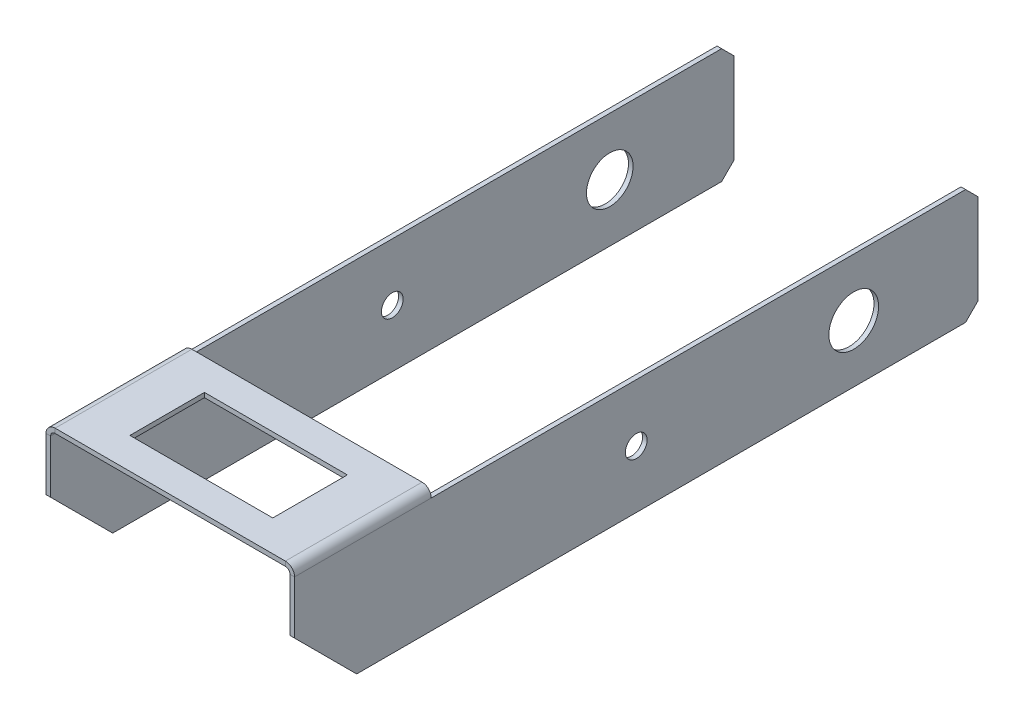
SolidWorks part; units mm, degrees
note: The reader was unsure of these and kept them because the rebuilt part matched: flange length of "Edge-Flange2".
ref_plane "Front Plane" through (0, 0, 0) normal (0, 0, 1) x (1, 0, 0)
ref_plane "Top Plane" through (0, 0, 0) normal (0, 1, 0) x (1, 0, 0)
ref_plane "Right Plane" through (0, 0, 0) normal (1, 0, 0) x (0, 0, -1)
sketch "Sketch1" plane through (0, 0, 0) normal (0, 1, 0) x (1, 0, 0)
  line L1 (-20, -11) -> (20, -11)
  line L2 (-20, -11) -> (-20, 11)
  line L3 (-20, 11) -> (20, 11)
  line L4 (20, -11) -> (20, 11)
  line L5 (-20, -11) -> (20, 11) construction
  line L6 (-20, 11) -> (20, -11) construction
  point P0 (0, 0)
  dimension "D1" = 40
  dimension "D2" = 22
base flange "Base-Flange2" sketch "Sketch1" thickness 0.7366 reverse thickness direction yes parameters "D1"=0.7366
edge flange "Edge-Flange2" sketch "Sketch30" flange profiles "Sketch30", "Sketch31" flange angle 90 flange length 20 flange position material inside bend radius 0.7366 thickness 0.7366 relief rectangular parameters "D6"=10, "D8"=1
sketch "Sketch30" plane through (20, 0, 0) normal (-1, 0, 0) x (0, 0, -1)
  line L2 (-11, 0) -> (-11, 19.2634)
  line L3 (-11, 19.2634) -> (99, 19.2634)
  line L4 (99, 19.2634) -> (99, 0)
  line L5 (11, 0) -> (-11, 0) construction
  line L6 (99, 0) -> (-11, 0)
  dimension "D1" = 110
sketch "Sketch31" plane through (-20, 0, 0) normal (1, 0, 0) x (0, 0, 1)
  line L0 (11, 0) -> (-11, 0) construction
  line L1 (11, 0) -> (-99, 0)
  line L2 (11, 0) -> (11, 19.2634)
  line L3 (11, 19.2634) -> (-99, 19.2634)
  line L4 (-99, 19.2634) -> (-99, 0)
  dimension "D1" = 110
bend "EdgeBend3" bend radius 0.7366 bend angle 90 parameters "D5"=1
bend "EdgeBend4" bend radius 0.7366 bend angle 90 parameters "D5"=2
sketch "Sketch32" plane through (-20, 0, 0) normal (-1, 0, 0) x (0, 0, 1)
  line L0 (-99, -19.2634) -> (-99, -0.7366) construction
  line L1 (-99, -10) -> (11, -10) construction
  line L2 (11, -0.7366) -> (11, -19.2634) construction
  circle A0 centre (-79, -10) radius 3.75
  circle A1 centre (-44, -10) radius 1.75
  dimension "D1" = 7.5
  dimension "D3" = 3.5
  dimension "D2" = 90
extrude "Cut-Extrude1" cut sketch "Sketch32" against normal blind 2 normal cut yes
sketch "Sketch33" plane through (20, 0, 0) normal (1, 0, 0) x (0, 0, -1)
  line L0 (99, -19.2634) -> (99, -0.7366) construction
  line L1 (99, -10) -> (-11, -10) construction
  line L2 (-11, -19.2634) -> (-11, -0.7366) construction
  circle A0 centre (44, -10) radius 1.75
  circle A1 centre (79, -10) radius 4
  dimension "D1" = 3.5
  dimension "D2" = 8
  dimension "D3" = 90
extrude "Cut-Extrude2" cut sketch "Sketch33" against normal blind 2 normal cut yes
chamfer "Chamfer1" distance 2 angle 45 4 edges at (-19.6317, -19.2634, -99) (19.6317, -19.2634, -99) (19.6317, -0.7366, -99) (-19.6317, -0.7366, -99)
chamfer "Chamfer2" distance 10 angle 45 2 edges at (-19.6317, -19.2634, 11) (19.6317, -19.2634, 11)
sketch "Sketch34" plane through (0, 0.7366, 0) normal (0, 1, 0) x (1, 0, 0)
  line L1 (-11.5, -6) -> (11.5, -6)
  line L2 (-11.5, -6) -> (-11.5, 6)
  line L3 (-11.5, 6) -> (11.5, 6)
  line L4 (11.5, -6) -> (11.5, 6)
  line L5 (-11.5, -6) -> (11.5, 6) construction
  line L6 (-11.5, 6) -> (11.5, -6) construction
  point P0 (0, 0)
  dimension "D1" = 23
  dimension "D2" = 12
extrude "Cut-Extrude3" cut sketch "Sketch34" against normal blind 2 normal cut yes
sketch "Bend-Lines3" [suppressed] plane through (0, 0, 0) normal (0, 1, 0) x (1, 0, 0)
sketch "Bounding-Box3" [suppressed] plane through (0, 0, 0) normal (0, 1, 0) x (1, 0, 0)
sheet metal parameters "Sheet-Metal4" thickness 0.7366 parameters "D1"=0.7366
flat pattern "Flat-Pattern4" [suppressed]
sketch "Bend-Lines4" plane through (0, 0, 0) normal (0, 1, 0) x (1, 0, 0)
sketch3d "Bounding-Box4" [suppressed]
  line L0 (20, 11, 0) -> (-20, 11, 0) construction
  line L1 (20, -11, 0) -> (-20, -11, 0) construction
  line L2 (20, 11, 0) -> (20, -11, 0) construction
  line L3 (-20, 11, 0) -> (-20, -11, 0) construction
sheet metal parameters "Sheet-Metal5" thickness 0.7366 parameters "D1"=0.7366
flat pattern "Flat-Pattern4"
sketch "Bend-Lines4" plane through (0, 0, 0) normal (0, -1, 0) x (-1, 0, 0)
  line L0 (19.3946, -11) -> (19.3946, 11) construction
  line L1 (-19.3946, 11) -> (-19.3946, -11) construction
  line L2 (19.3946, -11) -> (19.3946, 11) construction
  line L3 (-19.3946, 11) -> (-19.3946, -11) construction
sketch3d "Bounding-Box4" [suppressed]
  line L0 (38.7892, -11, 0) -> (38.7892, 99, 0) construction
  line L1 (-38.7892, -11, 0) -> (-38.7892, 99, 0) construction
  line L2 (38.7892, -11, 0) -> (-38.7892, -11, 0) construction
  line L3 (38.7892, 99, 0) -> (-38.7892, 99, 0) construction
bend of the flat pattern "Flatten-<EdgeBend3>1"
bend of the flat pattern "Flatten-<EdgeBend4>1"
sheet metal parameters "Sheet-Metal6" thickness 0.7366 parameters "D1"=0.7366
flat pattern "Flat-Pattern4"
sketch "Bend-Lines4" plane through (0, 0, 0) normal (0, -1, 0) x (-1, 0, 0)
  line L0 (19.3946, -11) -> (19.3946, 11) construction
  line L1 (-19.3946, 11) -> (-19.3946, -11) construction
  line L2 (19.3946, -11) -> (19.3946, 11) construction
  line L3 (-19.3946, 11) -> (-19.3946, -11) construction
sketch3d "Bounding-Box4" [suppressed]
  line L0 (38.7892, -11, 0) -> (38.7892, 99, 0) construction
  line L1 (-38.7892, -11, 0) -> (-38.7892, 99, 0) construction
  line L2 (38.7892, -11, 0) -> (-38.7892, -11, 0) construction
  line L3 (38.7892, 99, 0) -> (-38.7892, 99, 0) construction
bend of the flat pattern "Flatten-<EdgeBend3>1"
bend of the flat pattern "Flatten-<EdgeBend4>1"
sheet metal parameters "Sheet-Metal7" thickness 0.7366 parameters "D1"=0.7366
flat pattern "Flat-Pattern4"
sketch "Bend-Lines4" plane through (0, 0, 0) normal (0, -1, 0) x (-1, 0, 0)
  line L0 (19.3946, -11) -> (19.3946, 11) construction
  line L1 (-19.3946, 11) -> (-19.3946, -11) construction
  line L2 (19.3946, -11) -> (19.3946, 11) construction
  line L3 (-19.3946, 11) -> (-19.3946, -11) construction
sketch3d "Bounding-Box4" [suppressed]
  line L0 (38.7892, -11, 0) -> (38.7892, 99, 0) construction
  line L1 (-38.7892, -11, 0) -> (-38.7892, 99, 0) construction
  line L2 (38.7892, -11, 0) -> (-38.7892, -11, 0) construction
  line L3 (38.7892, 99, 0) -> (-38.7892, 99, 0) construction
bend of the flat pattern "Flatten-<EdgeBend3>1"
bend of the flat pattern "Flatten-<EdgeBend4>1"
sheet metal parameters "Sheet-Metal8" thickness 0.7366 parameters "D1"=0.7366
flat pattern "Flat-Pattern4"
sketch "Bend-Lines4" plane through (0, 0, 0) normal (0, -1, 0) x (-1, 0, 0)
  line L0 (19.3946, -11) -> (19.3946, 11) construction
  line L1 (-19.3946, 11) -> (-19.3946, -11) construction
  line L2 (19.3946, -11) -> (19.3946, 11) construction
  line L3 (-19.3946, 11) -> (-19.3946, -11) construction
sketch3d "Bounding-Box4" [suppressed]
  line L0 (38.7892, -11, 0) -> (38.7892, 99, 0) construction
  line L1 (-38.7892, -11, 0) -> (-38.7892, 99, 0) construction
  line L2 (38.7892, -11, 0) -> (-38.7892, -11, 0) construction
  line L3 (38.7892, 99, 0) -> (-38.7892, 99, 0) construction
bend of the flat pattern "Flatten-<EdgeBend3>1"
bend of the flat pattern "Flatten-<EdgeBend4>1"
